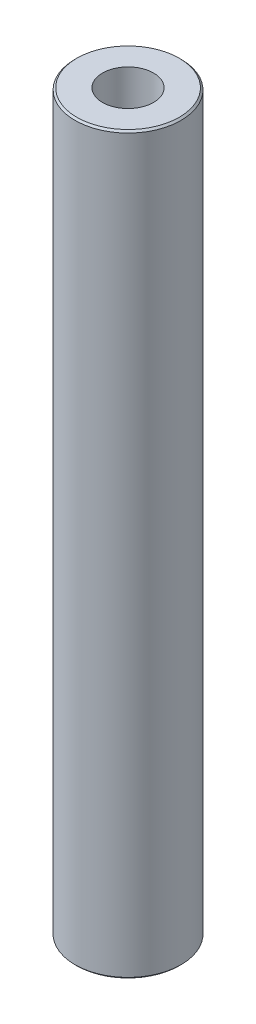
SolidWorks part; units mm, degrees
ref_plane "Front Plane" through (0, 0, 0) normal (0, 0, 1) x (1, 0, 0)
ref_plane "Top Plane" through (0, 0, 0) normal (0, 1, 0) x (1, 0, 0)
ref_plane "Right Plane" through (0, 0, 0) normal (1, 0, 0) x (0, 0, -1)
sketch "Sketch1" plane through (0, 0, 0) normal (0, 1, 0) x (1, 0, 0)
  circle A0 centre (0, 0) radius 15
  dimension "SHAFT_OD" = 30
extrude "Boss-Extrude1" add sketch "Sketch1" along normal blind 207.9522
sketch "Sketch2" plane through (0, 0, 0) normal (0, 1, 0) x (1, 0, 0)
  circle A0 centre (0, 0) radius 7.2252
  dimension "BORE_D" = 14.4503
extrude "Cut-Extrude1" cut sketch "Sketch2" along normal through all
chamfer "Chamfer1" distance 0.5092 angle 45 2 edges at (0, 207.9522, 15) (0, 0, 15)
